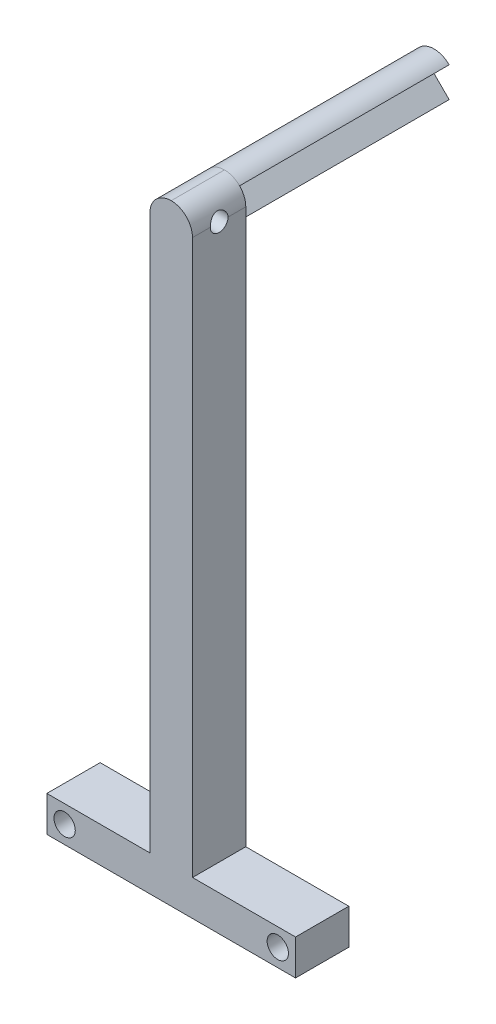
SolidWorks part; units mm, degrees
ref_plane "Plan de face" through (0, 0, 0) normal (0, 0, 1) x (1, 0, 0)
ref_plane "Plan de dessus" through (0, 0, 0) normal (0, 1, 0) x (1, 0, 0)
ref_plane "Plan de droite" through (0, 0, 0) normal (1, 0, 0) x (0, 0, -1)
sketch "Esquisse1" plane through (0, 0, 0) normal (0, 0, 1) x (1, 0, 0)
  line L0 (0, 0) -> (4.2426, 4.2426)
  line L1 (0, 0) -> (4.2426, -4.2426)
  line L2 (0, 0) -> (0, 6) construction
  circle A0 centre (0, 0) radius 6
  dimension "D1" = 12
  dimension "D2" = 45
extrude "Boss.-Extru.1" add sketch "Esquisse1" along normal blind 59 contours L1 L2 A0 | L2 L0 A0 region at (1.4917, 3.6013, 0) region at (-1.7388, -0.7203, 0)
sketch "Esquisse2" plane through (0, 0, 59) normal (0, 0, 1) x (1, 0, 0)
  line L1 (0, 6) -> (-6, 6)
  line L2 (4.2426, -4.2426) -> (0, 0)
  line L3 (0, 0) -> (4.2426, 4.2426)
  line L4 (4.2426, -4.2426) -> (0, 0)
  line L5 (0, 0) -> (4.2426, 4.2426)
  line L6 (0, 6) -> (0, -6)
  line L7 (0, -6) -> (-6, -6)
  line L8 (-6, 6) -> (-6, -6)
  line L9 (0, 6) -> (6, 6)
  line L10 (0, 6) -> (0, -6)
  line L11 (0, -6) -> (6, -6)
  line L12 (6, 6) -> (6, -6)
  arc A1 (4.2426, 4.2426) -> (4.2426, -4.2426) centre (0, 0) ccw
  arc A2 (4.2426, 4.2426) -> (4.2426, -4.2426) centre (0, 0) ccw
  line M8 (4.2426, -4.2426) -> (0, 0)
  line M9 (0, 0) -> (4.2426, 4.2426)
  arc M10 (4.2426, 4.2426) -> (4.2426, -4.2426) centre (0, 0) ccw
  dimension "D1" = 0
extrude "Boss.-Extru.2" add sketch "Esquisse2" along normal blind 15 contours L8 L7 M10 | L6 M10 | L6 M10 M9 | L12 L9 L11 M10 M9 M8 | L1 L8 M10 | L6 M8 M10 region at (-4.6598, 4.6598, 59) region at (1.4917, 3.6013, 59) region at (3.9753, 0, 59) region at (-2.5465, 0, 59) region at (1.4917, -3.6013, 59) region at (-4.6598, -4.6598, 59)
fillet "Congé1" radius 6 2 edges at (6, 6, 66.5) (-6, 6, 66.5)
sketch "Esquisse4" plane through (0, -6, 0) normal (0, -1, 0) x (1, 0, 0)
  line L5 (0, 59) -> (6, 59)
  line L6 (6, 59) -> (6, 74)
  line L7 (6, 74) -> (-6, 74)
  line L8 (-6, 74) -> (-6, 59)
  line L9 (-6, 59) -> (0, 59)
  line L10 (0, 59) -> (6, 59)
  line L11 (6, 59) -> (6, 74)
  line L12 (6, 74) -> (-6, 74)
  line L13 (-6, 74) -> (-6, 59)
  line L14 (-6, 59) -> (0, 59)
  dimension "D1" = 0
extrude "Boss.-Extru.3" add sketch "Esquisse4" along normal blind 150
sketch "Esquisse5" plane through (0, 0, 0) normal (1, 0, 0) x (0, 0, -1)
  line L0 (-59, -156) -> (-74, -156) construction
  line L1 (-59, -156) -> (-74, -156)
  line L3 (-74, -156) -> (-59, -156)
  line L4 (-74, -156) -> (-74, -166)
  line L5 (-74, -166) -> (-59, -166)
  line L6 (-59, -156) -> (-59, -166)
  dimension "D1" = 10
extrude "Boss.-Extru.4" add sketch "Esquisse5" along normal mid plane 70 contours L6 L1 L4 L5 region at (0, -161, 66.5)
sketch "Esquisse6" plane through (0, 0, 74) normal (0, 0, 1) x (1, 0, 0)
  line L0 (0, -166) -> (0, -156) construction
  line L1 (-35, -161) -> (0, -161) construction
  line L7 (6, -156) -> (6, 0)
  line L8 (-6, 0) -> (-6, -156)
  line L9 (-6, -156) -> (-35, -156)
  line L10 (-35, -156) -> (-35, -166)
  line L11 (-35, -166) -> (35, -166)
  line L12 (35, -166) -> (35, -156)
  line L13 (35, -156) -> (6, -156)
  line L14 (6, -156) -> (6, 0)
  line L15 (-6, 0) -> (-6, -156)
  line L16 (-6, -156) -> (-35, -156)
  line L17 (-35, -156) -> (-35, -166)
  line L18 (-35, -166) -> (35, -166)
  line L19 (35, -166) -> (35, -156)
  line L20 (35, -156) -> (6, -156)
  circle A0 centre (-30, -161) radius 3
  circle A1 centre (30, -161) radius 3
  arc A2 (6, 0) -> (0, 6) centre (0, 0) ccw
  arc A3 (0, 6) -> (-6, 0) centre (0, 0) ccw
  arc A4 (6, 0) -> (0, 6) centre (0, 0) ccw
  arc A5 (0, 6) -> (-6, 0) centre (0, 0) ccw
  dimension "D2" = 6
  dimension "D3" = 30
  dimension "D1" = 0
extrude "Enlèv. mat.-Extru.1" cut sketch "Esquisse6" against normal up to next contours A0 | A1 region at (-30, -161, 74) region at (30, -161, 74)
sketch "Esquisse7" plane through (6, 0, 0) normal (1, 0, 0) x (0, 0, -1)
  line L4 (-59, -156) -> (-59, 0)
  line L5 (-59, 0) -> (-74, 0)
  line L6 (-74, 0) -> (-74, -156)
  line L7 (-74, -156) -> (-59, -156)
  line L8 (-59, -156) -> (-59, 0)
  line L9 (-59, 0) -> (-74, 0)
  line L10 (-74, 0) -> (-74, -156)
  line L11 (-74, -156) -> (-59, -156)
  circle A0 centre (-66.5, 0) radius 2.5
  dimension "D2" = 5
  dimension "D1" = 0
extrude "Enlèv. mat.-Extru.2" cut sketch "Esquisse7" against normal up to next contours L9 A0 | L9 A0 region at (6, -1.061, 66.5) region at (6, 1.061, 66.5)
